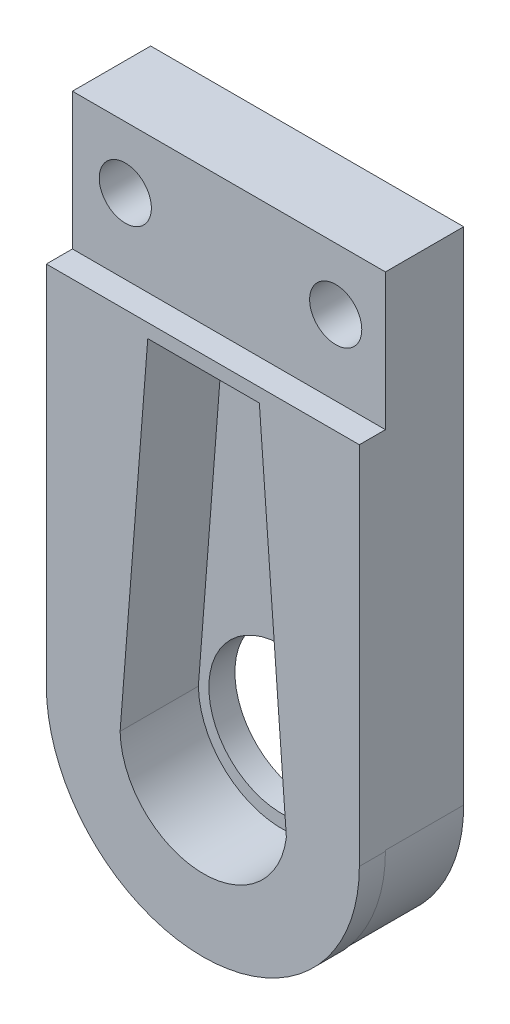
SolidWorks part; units mm, degrees
ref_plane "Front Plane" through (0, 0, 0) normal (0, 0, 1) x (1, 0, 0)
ref_plane "Top Plane" through (0, 0, 0) normal (0, 1, 0) x (1, 0, 0)
ref_plane "Right Plane" through (0, 0, 0) normal (1, 0, 0) x (0, 0, -1)
other "Graphic1"
other "object_1 (Open) -1"
ref_plane "Plane1" through (0, 0, 5) normal (0, 0, 1) x (1, 0, 0)
sketch "Sketch1" plane through (0, 0, 5) normal (0, 0, 1) x (1, 0, 0)
  line L1 (-60.0277, 110.2557) -> (-48.0277, 110.2557)
  line L2 (-60.0277, 110.2557) -> (-60.0277, 85.0557)
  line L3 (-60.0277, 85.0557) -> (-48.0277, 85.0557)
  line L4 (-48.0277, 110.2557) -> (-48.0277, 85.0557)
  dimension "D1" = 12
  dimension "D2" = 25.2
extrude "Boss-Extrude1" add sketch "Sketch1" along normal blind 3
fillet "Fillet1" radius 6 2 edges at (-48.0277, 85.0557, 6.5) (-60.0277, 85.0557, 6.5)
sketch "Sketch3" plane through (0, 0, 8) normal (0, 0, 1) x (1, 0, 0)
  line L1 (-60.0277, 105.018) -> (-48.0277, 105.018)
  line L2 (-60.0277, 105.018) -> (-60.0277, 85.018)
  line L3 (-60.0277, 85.018) -> (-48.0277, 85.018)
  line L4 (-48.0277, 105.018) -> (-48.0277, 85.018)
  dimension "D1" = 12
  dimension "D2" = 20
extrude "Boss-Extrude2" add sketch "Sketch3" along normal blind 1
fillet "Fillet2" radius 6 2 edges at (-48.0277, 85.018, 8.5) (-60.0277, 85.018, 8.5)
sketch "Sketch4" plane through (0, 0, 9) normal (0, 0, 1) x (1, 0, 0)
  line L0 (-56.1384, 104.486) -> (-51.8616, 104.486)
  line L1 (-51.8616, 104.486) -> (-50.8249, 90.587)
  line L2 (-56.1384, 104.486) -> (-57.1992, 90.915)
  arc A0 (-57.1992, 90.915) -> (-50.8249, 90.587) centre (-54, 90.9854) ccw
  point P10 (-50.8249, 90.3964)
extrude "Cut-Extrude1" cut sketch "Sketch4" against normal mid plane 6
sketch "Sketch5" plane through (0, 0, 6) normal (0, 0, 1) x (1, 0, 0)
  circle A0 centre (-53.9974, 91.082) radius 2.8
extrude "Cut-Extrude2" cut sketch "Sketch5" against normal through all
sketch "Sketch6" plane through (0, 0, 8) normal (0, 0, 1) x (1, 0, 0)
  circle A0 centre (-57.9999, 107.8868) radius 1
  circle A1 centre (-49.9341, 107.8868) radius 1
extrude "Cut-Extrude3" cut sketch "Sketch6" against normal through all
